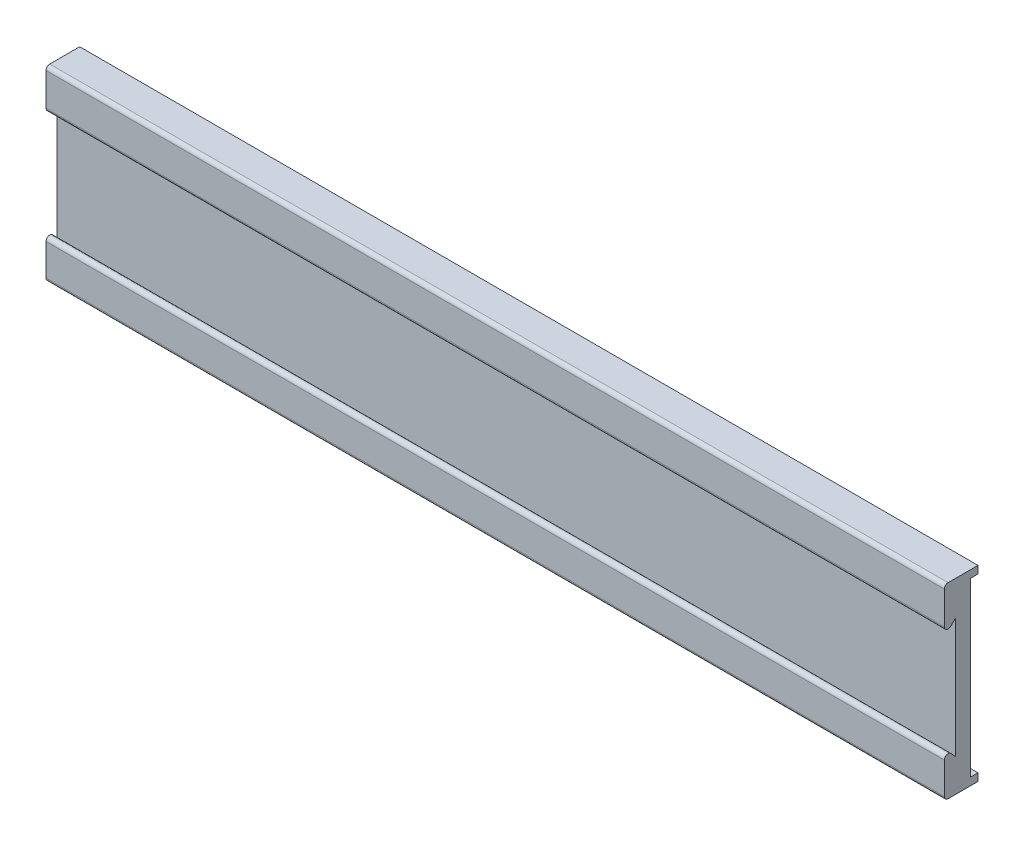
SolidWorks part; units mm, degrees
ref_plane "Front Plane" through (0, 0, 0) normal (0, 0, 1) x (1, 0, 0)
ref_plane "Top Plane" through (0, 0, 0) normal (0, 1, 0) x (1, 0, 0)
ref_plane "Right Plane" through (0, 0, 0) normal (1, 0, 0) x (0, 0, -1)
sketch "Sketch1" plane through (0, 0, 0) normal (0, 0, 1) x (1, 0, 0)
  line L0 (0, 24) -> (120, 24)
  line L1 (0, 0) -> (120, 0)
  line L2 (0, 0) -> (0, 25)
  line L3 (0, 25) -> (120, 25)
  line L4 (120, 0) -> (120, 25)
  line L5 (0, 12.5) -> (15.6687, 12.5) construction
  line L6 (0, 1) -> (120, 1)
  dimension "D1" = 25
  dimension "D2" = 120
  dimension "D3" = 1
extrude "Boss-Extrude1" add sketch "Sketch1" along normal blind 3.5 contours L0 L4 L3 L2 | L2 L6 L4 L0 | L6 L2 L1 L4 region at (60, 24.5, 0) region at (60, 12.5, 0) region at (60, 0.5, 0)
extrude "Boss-Extrude2" add sketch "Sketch1<3>" against normal blind 1 contours L0 L4 L3 L2 | L6 L2 L1 L4 region at (60, 24.5, 0) region at (60, 0.5, 0)
sketch "Sketch1<3>" plane through (0, 0, 0) normal (0, 0, 1) x (1, 0, 0) same geometry as "Sketch1"
sketch "Sketch3" plane through (120, 0, 0) normal (1, 0, 0) x (0, 0, -1)
  line L0 (-3.5, 24) -> (-2, 24)
  line L1 (-3.5, 0) -> (-3.5, 25) construction
  line L2 (-2, 24) -> (-2, 1)
  line L3 (-2, 1) -> (-3.5, 1)
  line L4 (-3.5, 6) -> (-2, 4.3743)
  line L5 (-3.5, 19) -> (-2, 20.384)
  point P10 (0, 0)
  line M10 (-3.5, 25) -> (-3.5, 0)
  dimension "D1" = 1.5
  dimension "D2" = 5
  dimension "D3" = 5
extrude "Cut-Extrude1" cut sketch "Sketch3" against normal through all contours L5 L4 L2 M10 region at (120, 12.4375, 2.7241)
fillet "Fillet1" radius 0.5 2 edges at (60, 19, 3.5) (60, 6, 3.5)
fillet "Fillet2" radius 0.5 2 edges at (60, 0, 3.5) (60, 25, 3.5)
